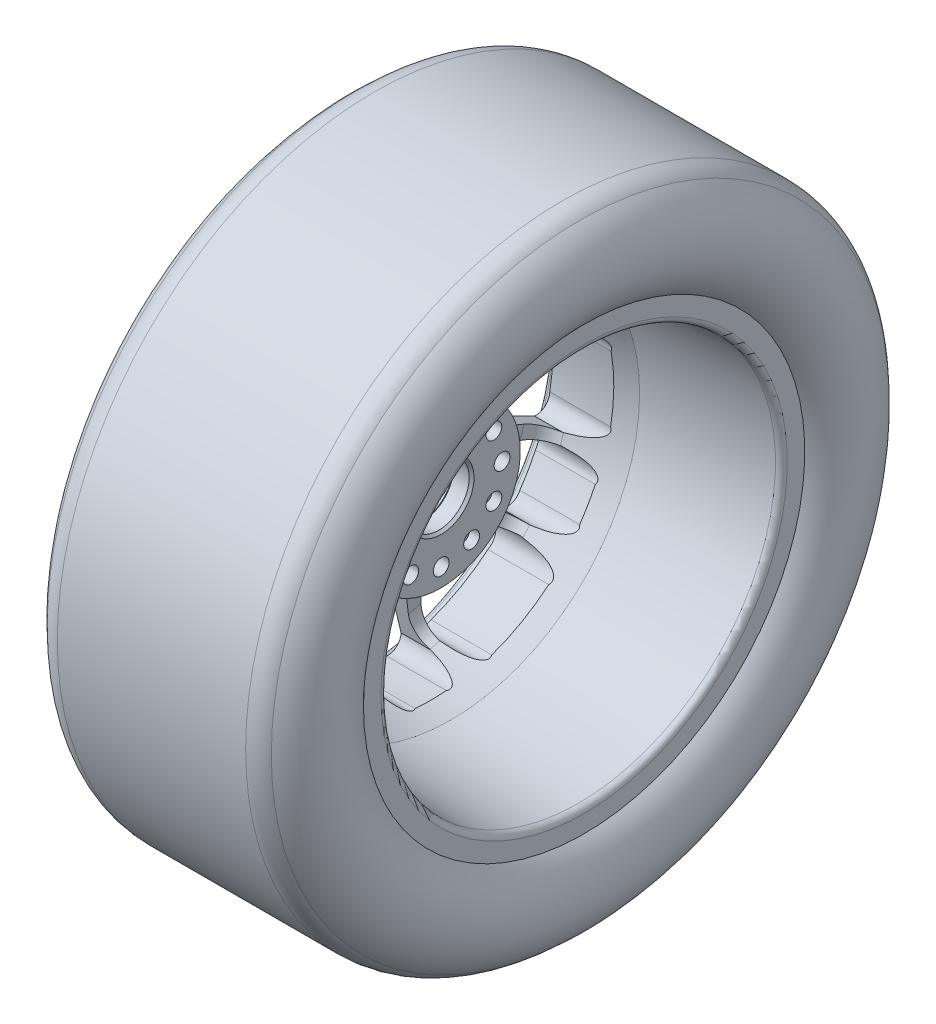
SolidWorks part; units mm, degrees
ref_plane "Front Plane" through (0, 0, 0) normal (0, 0, 1) x (1, 0, 0)
ref_plane "Top Plane" through (0, 0, 0) normal (0, 1, 0) x (1, 0, 0)
ref_plane "Right Plane" through (0, 0, 0) normal (1, 0, 0) x (0, 0, -1)
sketch "Sketch1" plane through (0, 0, 0) normal (0, 0, 1) x (1, 0, 0)
  line L0 (35.4045, 491.5563) -> (35.4045, 426.5563)
  line L1 (18.4047, 426.5563) -> (35.4045, 426.5563)
  line L2 (18.4047, 426.5563) -> (18.4047, 472.3568)
  line L3 (10.7798, 482.0706) -> (-14.7415, 488.3106)
  line L4 (-26.1584, 503.6667) -> (-21.9454, 584.0233)
  line L5 (35.4045, 491.5563) -> (4.2122, 500.3382)
  line L6 (-10.1726, 517.8128) -> (-12.6873, 546.5441)
  line L7 (-34.3533, 588.5361) -> (-24.5228, 587.151)
  line L8 (-37.7953, 607.6163) -> (-37.7953, 592.4969)
  line L9 (-31.9953, 597.2459) -> (-31.9953, 601.4825)
  line L10 (-26.1531, 590.8702) -> (-15.2005, 589.912)
  line L11 (0.8416, 567.238) -> (43.5102, 581.4566)
  line L12 (57.5047, 686.6163) -> (-19.839, 686.6163)
  line L13 (2.7073, 571.988) -> (40.3604, 583.1335)
  line L14 (42.6, 583.7208) -> (53.5021, 584.6831)
  line L15 (53.5021, 584.6831) -> (115.8217, 588.7335)
  line L16 (-11.181, 590.5134) -> (-8.7791, 588.1115)
  line L17 (43.5102, 581.4566) -> (148.1291, 588.4274)
  line L18 (-7.6161, 586.286) -> (-3.5221, 575.0378)
  line L19 (40.3604, 583.1335) -> (42.6, 583.7208)
  line L20 (152.8048, 607.7926) -> (152.8048, 593.4169)
  line L21 (124.0048, 590.9063) -> (126.4855, 590.9063)
  line L22 (130.01, 589.912) -> (140.9626, 590.8702)
  line L23 (146.8048, 600.0333) -> (146.8048, 597.2458)
  line L25 (57.5047, 686.6163) -> (134.8497, 686.6163)
  arc A0 (-10.1726, 517.8128) -> (4.2122, 500.3382) centre (9.5839, 519.418) ccw
  arc A1 (-24.5228, 587.151) -> (-21.9454, 584.0233) centre (-24.798, 584.2984) cw
  arc A2 (-37.7953, 592.4969) -> (-34.3533, 588.5361) centre (-34.0939, 592.2375) ccw
  arc A3 (-37.7953, 607.6163) -> (-34.0161, 607.4087) centre (-36.0095, 605.6229) cw
  arc A4 (-31.9953, 601.4825) -> (-34.0161, 607.4087) centre (-40.376, 601.9323) ccw
  arc A5 (-31.9953, 597.2459) -> (-26.1531, 590.8702) centre (-25.8863, 596.9791) ccw
  arc A6 (-15.2005, 589.912) -> (-12.5515, 590.6244) centre (-14.7139, 593.3837) ccw
  arc A7 (-12.5515, 590.6244) -> (-11.181, 590.5134) centre (-11.9217, 589.8837) cw
  arc A8 (-8.7791, 588.1115) -> (-7.6161, 586.286) centre (-14.4183, 583.2357) cw
  arc A9 (-3.5221, 575.0378) -> (2.7073, 571.988) centre (1.1175, 576.6276) ccw
  arc A10 (115.8217, 588.7335) -> (119.22, 589.6445) centre (115.9759, 594.9525) ccw
  arc A11 (119.22, 589.6445) -> (124.0048, 590.9063) centre (123.7209, 582.2801) cw
  arc A12 (126.4855, 590.9063) -> (127.3516, 590.631) centre (126.5674, 589.6642) cw
  arc A13 (127.3516, 590.631) -> (130.01, 589.912) centre (129.6488, 593.8504) ccw
  arc A14 (140.9626, 590.8702) -> (146.8048, 597.2458) centre (140.6958, 596.9791) ccw
  arc A15 (146.8048, 600.0333) -> (150.4846, 607.639) centre (157.2201, 599.6872) cw
  arc A16 (150.4846, 607.639) -> (152.8048, 607.7926) centre (151.7215, 606.5557) cw
  arc A17 (152.8048, 593.4169) -> (148.1291, 588.4274) centre (147.9722, 593.26) cw
  arc A18 (152.8048, 607.7926) -> (149.5453, 680.1824) centre (119.1881, 642.5472) ccw
  arc A19 (-37.7953, 607.6163) -> (-34.5324, 680.1847) centre (-3.8872, 642.4492) cw
  arc A20 (-19.839, 686.6163) -> (-34.5324, 680.1847) centre (-19.839, 666.6163) ccw
  arc A21 (134.8497, 686.6163) -> (149.5453, 680.1824) centre (134.8497, 666.6163) cw
  arc A317 (0.8416, 567.238) -> (-12.6873, 546.5441) centre (7.2366, 548.2879) ccw
  spline S0 degree 2 poles (18.4047, 472.3568) (17.7577, 479.7029) (10.7798, 482.0706) knots 0 0 0 1 1 1
  spline S1 degree 2 poles (-26.1584, 503.6667) (-25.9832, 491.8748) (-14.7415, 488.3106) knots 0 0 0 1 1 1
  point P1 (-23.2166, 493.9317)
  point P7 (4.2122, 500.3382)
  point P26 (57.5047, 686.6163)
revolve "Revolve2" add sketch "Sketch1" angle 360 about L1
ref_plane "Plane1" through (-37.7953, 0, 0) normal (-1, 0, 0) x (0, 0, 1)
sketch "Sketch4" plane through (-37.7953, 0, 0) normal (-1, 0, 0) x (0, 0, 1)
  line L0 (-26.0705, 250.9482) -> (563.9295, 250.9482) construction
  line L1 (91.2555, 445.5417) -> (134.9711, 465.9346)
  line L2 (90.8651, 408.5008) -> (134.1411, 387.191)
  line L3 (89.7059, 459.4857) -> (132.805, 474.0297)
  line L4 (73.3706, 487.7792) -> (107.5156, 517.8322)
  line L5 (62.0695, 357.0194) -> (101.5881, 329.3571)
  line L6 (29.796, 338.8371) -> (32.9792, 290.7041)
  line L7 (73.3706, 365.3335) -> (107.5156, 335.2805)
  line L8 (89.7059, 393.627) -> (132.805, 379.083)
  line L9 (-29.186, 338.0341) -> (-33.383, 289.9788)
  line L10 (-61.0691, 356.8926) -> (-101.1619, 330.0694)
  line L11 (-16.3353, 332.4041) -> (-25.2894, 287.8071)
  line L12 (16.3353, 332.4041) -> (25.2894, 287.8071)
  line L13 (-91.2555, 407.571) -> (-134.9711, 387.1781)
  line L14 (-90.8651, 444.6118) -> (-134.1411, 465.9217)
  line L15 (-89.7059, 393.627) -> (-132.805, 379.083)
  line L16 (-73.3706, 365.3335) -> (-107.5156, 335.2805)
  line L17 (-62.0695, 496.0933) -> (-101.5881, 523.7556)
  line L18 (-29.796, 514.2756) -> (-32.9792, 562.4086)
  line L19 (-73.3706, 487.7792) -> (-107.5156, 517.8322)
  line L20 (-89.7059, 459.4857) -> (-132.805, 474.0297)
  line L45 (16.3353, 520.7086) -> (25.2894, 565.3056)
  line L47 (-16.3353, 520.7086) -> (-25.2894, 565.3056)
  line L48 (29.186, 515.0786) -> (33.383, 563.1338)
  line L51 (61.0691, 496.2201) -> (101.1619, 523.0433)
  line L52 (-11.5208, 522.1294) -> (-20.3502, 566.1053) construction
  line L53 (11.5208, 522.1294) -> (20.3502, 566.1053) construction
  line L54 (34.2372, 515.4464) -> (38.275, 561.6798) construction
  line L55 (58.9586, 500.8239) -> (97.5315, 526.6302) construction
  arc A0 (12.8389, 575.3197) -> (-12.8389, 575.3197) centre (0, 426.5563) ccw
  arc A1 (-25.2894, 565.3056) -> (-12.8389, 575.3197) centre (-14.0571, 564.0874) cw
  arc A2 (25.2894, 565.3056) -> (12.8389, 575.3197) centre (14.0571, 564.0874) ccw
  arc A3 (99.6376, 544.7678) -> (50.3523, 572.7283) centre (0, 426.5563) ccw construction
  arc A4 (96.166, 541.1542) -> (49.3609, 567.7799) centre (0, 426.5563) ccw
  arc A5 (33.383, 563.1338) -> (49.3609, 567.7799) centre (43.6949, 557.4679) cw
  arc A6 (101.1619, 523.0433) -> (96.166, 541.1542) centre (89.6085, 529.6008) ccw
  arc A7 (134.1411, 387.191) -> (147.3277, 400.5731) centre (134.0434, 400.4753) ccw
  arc A8 (147.3277, 400.5731) -> (146.9836, 454.4203) centre (0, 426.5563) ccw
  arc A9 (134.9711, 465.9346) -> (146.9836, 454.4203) centre (135.2202, 454.1712) cw
  arc A10 (91.2555, 445.5417) -> (90.8651, 408.5008) centre (108.3087, 426.8394) ccw
  arc A11 (73.3706, 487.7792) -> (89.7059, 459.4857) centre (86.8952, 476.7253) ccw
  arc A12 (135.2523, 489.8191) -> (122.4133, 512.0568) centre (0, 426.5563) ccw
  arc A13 (107.5156, 517.8322) -> (122.4133, 512.0568) centre (112.0768, 507.4957) cw
  arc A14 (132.805, 474.0297) -> (135.2523, 489.8191) centre (126.1339, 483.148) ccw
  arc A15 (32.9792, 290.7041) -> (51.1617, 285.9752) centre (44.4349, 297.4309) ccw
  arc A16 (51.1617, 285.9752) -> (97.6227, 313.1968) centre (0, 426.5563) ccw
  arc A17 (101.5881, 329.3571) -> (97.6227, 313.1968) centre (91.5253, 323.2596) cw
  arc A18 (62.0695, 357.0194) -> (29.796, 338.8371) centre (54.3995, 332.8998) ccw
  arc A19 (89.7059, 393.627) -> (73.3706, 365.3335) centre (86.8952, 376.3874) ccw
  arc A20 (122.4133, 341.0558) -> (135.2523, 363.2935) centre (0, 426.5563) ccw
  arc A21 (132.805, 379.083) -> (135.2523, 363.2935) centre (126.1339, 369.9646) cw
  arc A22 (107.5156, 335.2805) -> (122.4133, 341.0558) centre (112.0768, 345.617) ccw
  arc A23 (-101.1619, 330.0694) -> (-96.166, 311.9584) centre (-89.6085, 323.5119) ccw
  arc A24 (-96.166, 311.9584) -> (-49.3609, 285.3328) centre (0, 426.5563) ccw
  arc A25 (-33.383, 289.9788) -> (-49.3609, 285.3328) centre (-43.6949, 295.6448) cw
  arc A26 (-29.186, 338.0341) -> (-61.0691, 356.8926) centre (-53.9091, 332.6167) ccw
  arc A27 (16.3353, 332.4041) -> (-16.3353, 332.4041) centre (0, 326.2184) ccw
  arc A28 (-12.8389, 277.793) -> (12.8389, 277.793) centre (0, 426.5563) ccw
  arc A29 (25.2894, 287.8071) -> (12.8389, 277.793) centre (14.0571, 289.0253) cw
  arc A30 (-25.2894, 287.8071) -> (-12.8389, 277.793) centre (-14.0571, 289.0253) ccw
  arc A31 (-134.1411, 465.9217) -> (-147.3277, 452.5396) centre (-134.0434, 452.6373) ccw
  arc A32 (-147.3277, 452.5396) -> (-146.9836, 398.6923) centre (0, 426.5563) ccw
  arc A33 (-134.9711, 387.1781) -> (-146.9836, 398.6923) centre (-135.2202, 398.9415) cw
  arc A34 (-91.2555, 407.571) -> (-90.8651, 444.6118) centre (-108.3087, 426.2732) ccw
  arc A35 (-73.3706, 365.3335) -> (-89.7059, 393.627) centre (-86.8952, 376.3874) ccw
  arc A36 (-135.2523, 363.2935) -> (-122.4133, 341.0558) centre (0, 426.5563) ccw
  arc A37 (-107.5156, 335.2805) -> (-122.4133, 341.0558) centre (-112.0768, 345.617) cw
  arc A38 (-16.3353, 520.7086) -> (16.3353, 520.7086) centre (0, 526.8942) ccw
  arc A39 (-132.805, 379.083) -> (-135.2523, 363.2935) centre (-126.1339, 369.9646) ccw
  arc A40 (-32.9792, 562.4086) -> (-51.1617, 567.1375) centre (-44.4349, 555.6818) ccw
  arc A41 (29.186, 515.0786) -> (61.0691, 496.2201) centre (53.9091, 520.4959) ccw
  arc A42 (-51.1617, 567.1375) -> (-97.6227, 539.9159) centre (0, 426.5563) ccw
  arc A43 (-101.5881, 523.7556) -> (-97.6227, 539.9159) centre (-91.5253, 529.853) cw
  arc A44 (-62.0695, 496.0933) -> (-29.796, 514.2756) centre (-54.3995, 520.2128) ccw
  arc A45 (-89.7059, 459.4857) -> (-73.3706, 487.7792) centre (-86.8952, 476.7253) ccw
  arc A46 (-122.4133, 512.0568) -> (-135.2523, 489.8191) centre (0, 426.5563) ccw
  arc A47 (-132.805, 474.0297) -> (-135.2523, 489.8191) centre (-126.1339, 483.148) cw
  arc A48 (-107.5156, 517.8322) -> (-122.4133, 512.0568) centre (-112.0768, 507.4957) ccw
  arc A83 (-11.5208, 522.1294) -> (11.5208, 522.1294) centre (0, 526.8942) ccw construction
  arc A84 (20.3502, 566.1053) -> (12.8389, 575.3197) centre (12.0917, 567.0419) ccw construction
  arc A85 (-20.3502, 566.1053) -> (-12.8389, 575.3197) centre (-12.0917, 567.0419) cw construction
  arc A86 (-25.2894, 565.3056) -> (-13.2776, 580.3004) centre (-12.0917, 567.0419) cw construction
  arc A87 (13.2776, 580.3004) -> (-13.2776, 580.3004) centre (0, 426.5563) ccw construction
  arc A88 (25.2894, 565.3056) -> (13.2776, 580.3004) centre (12.0917, 567.0419) ccw construction
  arc A89 (33.383, 563.1338) -> (50.3523, 572.7283) centre (48.9168, 555.4636) cw construction
  arc A90 (101.1619, 523.0433) -> (99.6376, 544.7678) centre (86.9583, 532.9624) ccw construction
  arc A91 (97.5315, 526.6302) -> (96.166, 541.1542) centre (86.9583, 532.9624) ccw construction
  arc A92 (38.275, 561.6798) -> (49.3609, 567.7799) centre (48.9168, 555.4636) cw construction
  arc A93 (34.2372, 515.4464) -> (58.9586, 500.8239) centre (53.9091, 520.4959) ccw construction
  point P13 (0, 575.3004)
  point P123 (0, 426.5563)
  point P124 (0, 426.5563)
  dimension "D1" = 5
  dimension "D2" = 6
extrude "Cut-Extrude2" cut sketch "Sketch4" against normal through all contours A42 | L9 L12 | L5 L7 | L18 | L14 | L19 A48 A46 A47 L20 A45 | L13 A34 L14 A31 A32 A33 | L17 A44 L18 A40 A42 A43 | L47 A38 L45 A2 A0 A1 | L48 A41 L51 A6 A4 A5 | L3 A14 A12 A13 L4 A11 | L1 A10 L2 A7 A8 A9 | L7 A22 A20 A21 L8 A19 | L5 A18 L6 A15 A16 A17 | L11 A30 A28 A29 L12 A27 | L15 A39 A36 A37 L16 A35 | L9 A25 A24 A23 L10 A26 region at (-37.7953, 426.6504, 120.8939) region at (-37.7953, 486.3927, 103.6396) region at (-37.7953, 321.9062, 60.5284) region at (-37.7953, 366.72, 103.6396) region at (-37.7953, 306.8837, 0) region at (-37.7953, 426.4623, -120.8939) region at (-37.7953, 366.72, -103.6396) region at (-37.7953, 531.2065, -60.5284) region at (-37.7953, 486.3927, -103.6396) region at (-37.7953, 546.229, 0) region at (-37.7953, 531.3005, 60.3655)
fillet "Fillet1" [suppressed] radius 2
fillet "Fillet2" [suppressed] radius 2
fillet "Fillet3" [suppressed] radius 2
fillet "Fillet4" [suppressed] radius 2
sketch "Sketch5" plane through (18.4047, 0, 0) normal (-1, 0, 0) x (0, 0, 1)
  circle A0 centre (0, 426.5563) radius 25
extrude "Cut-Extrude3" cut sketch "Sketch5" against normal blind 30
chamfer "Chamfer1" distance 2 angle 45 2 edges at (35.4045, 426.5563, -25) (18.4047, 426.5563, 25)
sketch "Sketch6" plane through (-37.7953, 0, 0) normal (-1, 0, 0) x (0, 0, 1)
  arc A0 (6.4863, 376.9788) -> (49.5775, 420.0701) centre (0, 426.5563) ccw
  circle A1 centre (50, 426.5563) radius 6.5
  circle A2 centre (0, 376.5563) radius 6.5
  circle A3 centre (-50, 426.5563) radius 6.5
  circle A4 centre (0, 476.5563) radius 6.5
  arc A5 (49.5775, 433.0426) -> (6.4863, 476.1338) centre (0, 426.5563) ccw
  arc A6 (-6.4863, 476.1338) -> (-49.5775, 433.0426) centre (0, 426.5563) ccw
  arc A7 (-49.5775, 420.0701) -> (-6.4863, 376.9788) centre (0, 426.5563) ccw
  point P14 (0, 426.5563)
  dimension "D1" = 4
extrude "Cut-Extrude5" cut sketch "Sketch6" against normal blind 150 contours A1 | A4 | A2 | A3 region at (-37.7953, 376.5563, 0) region at (-37.7953, 426.5563, 50) region at (-37.7953, 426.5563, -50) region at (-37.7953, 476.5563, 0)
sketch "Sketch7" plane through (35.4045, 0, 0) normal (1, 0, 0) x (0, 0, -1)
  circle A1 centre (-43.3013, 451.5563) radius 6.5
  circle A2 centre (-25, 469.8576) radius 6.5
  circle A3 centre (43.3013, 451.5563) radius 6.5
  circle A4 centre (25, 469.8576) radius 6.5
  circle A5 centre (25, 383.2551) radius 6.5
  circle A6 centre (43.3013, 401.5563) radius 6.5
  circle A7 centre (-43.3013, 401.5563) radius 6.5
  circle A8 centre (-25, 383.2551) radius 6.5
  point P26 (0, 426.5563)
  dimension "D3" = 4
extrude "Cut-Extrude6" cut sketch "Sketch7" against normal blind 8
ref_plane "Plane2" through (18.4047, 0, 0) normal (-1, 0, 0) x (0, 0, 1)
sketch "Sketch9" plane through (18.4047, 0, 0) normal (-1, 0, 0) x (0, 0, 1)
  circle A0 centre (50, 426.5563) radius 7.5
  circle A1 centre (0, 376.5563) radius 7.5
  circle A2 centre (-50, 426.5563) radius 7.5
  circle A3 centre (0, 476.5563) radius 7.5
  point P12 (0, 426.5563)
  dimension "D1" = 4
extrude "Cut-Extrude7" cut sketch "Sketch9" along normal blind 120
fillet "Fillet5" radius 2 4 edges at (18.4047, 426.5563, 57.5) (18.4047, 484.0563, 0) (18.4047, 426.5563, -57.5) (18.4047, 369.0563, 0)
sketch "Sketch10" plane through (0, 0, 0) normal (1, 0, 0) x (0, 0, -1)
  line L0 (0, 686.6163) -> (0, 166.4964)
  circle A0 centre (0, 426.5563) radius 260.0599 construction
ref_point "Point1"
sketch "Sketch11" plane through (0, 0, 0) normal (0, 0, 1) x (1, 0, 0)
  line L0 (-19.839, 166.4964) -> (134.8497, 166.4964) construction
  point P0 (57.5054, 166.4964)
ref_point "Point2"
